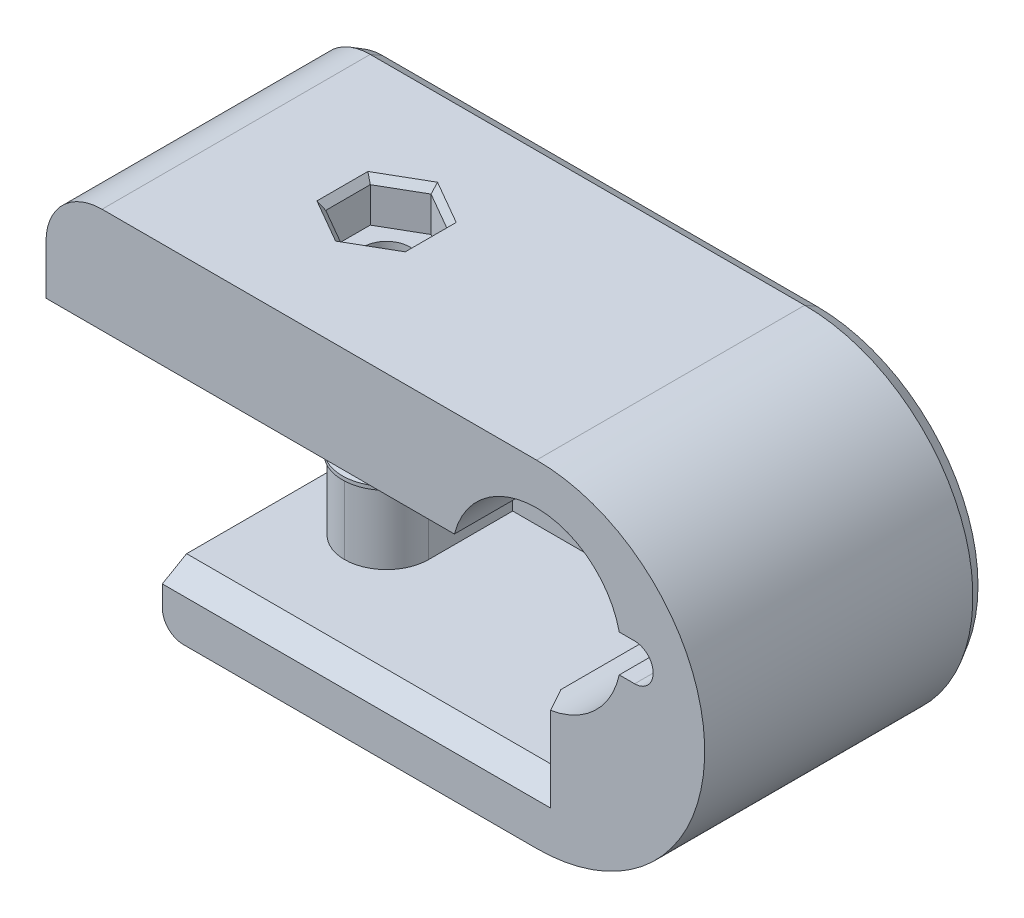
SolidWorks part; units mm, degrees
material "Custom Plastic"
ref_plane "Front Plane" through (0, 0, 0) normal (0, 0, 1) x (1, 0, 0)
ref_plane "Top Plane" through (0, 0, 0) normal (0, 1, 0) x (1, 0, 0)
ref_plane "Right Plane" through (0, 0, 0) normal (1, 0, 0) x (0, 0, -1)
sketch "Sketch1" plane through (0, 0, 0) normal (0, 0, 1) x (1, 0, 0)
  line L0 (5.9035, -1.3233) -> (7, -1.3233)
  line L1 (0, 9) -> (-31, 9)
  line L3 (0, -15) -> (-26.7, -15)
  line L4 (-26.7, -6) -> (-26.7, -15)
  line L5 (-41.6611, -6) -> (7.1, -6) construction
  line L6 (-41.6611, -6) -> (-41.6611, -11) construction
  line L7 (-41.6611, -11) -> (7.1, -11) construction
  line L8 (7.1, -6) -> (7.1, -11) construction
  line L9 (-20, 15.6207) -> (-20, -19.311) construction
  line L10 (7, 1.3233) -> (5.9035, 1.3233)
  line L11 (-25, -4.25) -> (-15, -4.25) construction
  line L12 (-25, -4.25) -> (-25, -0.25) construction
  line L13 (-15, -4.25) -> (-15, -0.25) construction
  line L14 (-25, -0.25) -> (-15, -0.25) construction
  line L15 (-25, -4.25) -> (-15, -0.25) construction
  line L16 (-15, -4.25) -> (-25, -0.25) construction
  line L17 (-5.8611, -1.5) -> (-10.9, -6)
  line L18 (-10.9, -6) -> (-26.7, -6)
  line L20 (-5.8611, 1.5) -> (-35, 1.5)
  line L21 (-35, 1.5) -> (-35, 5)
  arc A0 (5.9035, 1.3233) -> (-5.8611, 1.5) centre (0, 0) ccw
  arc A1 (7, -1.3233) -> (7, 1.3233) centre (7, 0) ccw
  arc A2 (-5.8611, -1.5) -> (5.9035, -1.3233) centre (0, 0) ccw
  arc A3 (0, -15) -> (0, 9) centre (0, -3) ccw
  arc A4 (-31, 9) -> (-35, 5) centre (-31, 5) ccw
  point P18 (-20, -2.25)
  dimension "D1" = 12.1
  dimension "D12" = 12
  dimension "D16" = 4
  dimension "D3" = 5
  dimension "D4" = 7.1
  dimension "D5" = 20
  dimension "D6" = 4
  dimension "D7" = 10
  dimension "D8" = 1.75
  dimension "D9" = 4
  dimension "D10" = 10.9
  dimension "D11" = 1.75
  dimension "D13" = 7
  dimension "D14" = 35
  dimension "D15" = 1.7
  dimension "D2" = 6
extrude "Boss-Extrude1" add sketch "Sketch1" along normal blind 20
sketch "Sketch2" plane through (0, 0, 20) normal (0, 0, 1) x (1, 0, 0)
  line L0 (-26.7, -6) -> (-26.7, -15) construction
  line L1 (-26.7, -6) -> (-23.7, -6)
  line L2 (-26.7, -6) -> (-26.7, -11)
  line L3 (-26.7, -11) -> (-23.7, -11)
  line L6 (-20.7, -18.4336) -> (-20.7, 0) construction
  line L7 (-17.7, -11) -> (-17.7, -6)
  line L8 (-23.7, -11) -> (-23.7, -6)
  line L9 (-17.7, -11) -> (0, -11)
  line L10 (-17.7, -18.4336) -> (-17.7, 0) construction
  line L11 (-23.7, -18.4336) -> (-23.7, 0) construction
  line L12 (-17.7, -6) -> (-10.9, -6)
  line L14 (0, 0) -> (-5.8611, -1.5)
  line L15 (-5.8611, -1.5) -> (-10.9, -6)
  line L16 (0, 0) -> (0, -11)
  dimension "D4" = 20.7
  dimension "D1" = 5
  dimension "D5" = 3
  dimension "D6" = 3
extrude "Cut-Extrude1" cut sketch "Sketch2" against normal offset from surface (16 mm away) 4 up to face at (-9.8986, -1.1908, 0)
sketch "Sketch3" plane through (0, 0, 20) normal (0, 0, 1) x (1, 0, 0)
  line L1 (-23.7, -11) -> (-17.7, -11)
  line L2 (-23.7, -11) -> (-23.7, -6)
  line L3 (-23.7, -6) -> (-17.7, -6)
  line L4 (-17.7, -11) -> (-17.7, -6)
extrude "Cut-Extrude2" cut sketch "Sketch3" against normal blind 7
fillet "Fillet1" radius 3 2 edges at (-17.7, -8.5, 13) (-23.7, -8.5, 13)
sketch "Sketch4" plane through (-1.2719, 0, 0) normal (0, 1, 0) x (1, 0, 0)
  circle A0 centre (-19.4281, -10) radius 1.65
  circle A1 centre (-19.4281, -10) radius 3 construction
  dimension "D1" = 3.3
extrude "Cut-Extrude3" cut sketch "Sketch4" against normal through all and the other way through all
sketch "Sketch5" plane through (-1.2719, 0, 0) normal (0, 1, 0) x (1, 0, 0)
  line L1 (-19.4281, -13.1754) -> (-16.6781, -11.5877)
  line L2 (-16.6781, -11.5877) -> (-16.6781, -8.4123)
  line L3 (-16.6781, -8.4123) -> (-19.4281, -6.8246)
  line L4 (-19.4281, -6.8246) -> (-22.1781, -8.4123)
  line L5 (-22.1781, -8.4123) -> (-22.1781, -11.5877)
  line L6 (-22.1781, -11.5877) -> (-19.4281, -13.1754)
  circle A0 centre (-19.4281, -10) radius 2.75 construction
  circle A1 centre (-19.4281, -10) radius 1.65 construction
  dimension "D1" = 5.5
extrude "Cut-Extrude4" cut sketch "Sketch5" against normal offset from surface (10 mm away) 21 from offset 16 up to face at (-20.7, -15, 11.65)
fillet "Fillet2" [suppressed] radius 12
fillet "Fillet3" radius 1.5 1 edges at (-26.7, -15, 10)
sketch "Sketch6" plane through (0, 1.5, 0) normal (0, -1, 0) x (1, 0, 0)
  line L0 (-17.7, 2.476) -> (-17.7, 5.8757) construction
  line L1 (-17.7, 4) -> (-17.7, 10) construction
  line L2 (-23.7, 2.476) -> (-23.7, 5.8757) construction
  line L3 (-23.7, 4) -> (-23.7, 10) construction
  circle A0 centre (-20.7, 10) radius 3.15
  circle A1 centre (-20.7, 10) radius 1.65
  circle A2 centre (-20.7, 10) radius 1.65 construction
  arc A3 (-23.7, 5.8757) -> (-17.7, 5.8757) centre (-20.7, 10) ccw construction
  arc A4 (-23.7, 2.476) -> (-17.7, 2.476) centre (-20.7, 10) ccw construction
  dimension "D1" = 1.5
  dimension "D2" = 5.1
  dimension "D3" = 3
extrude "Boss-Extrude2" add sketch "Sketch6" along normal blind 1.75
sketch "Sketch7" plane through (0, -6, 0) normal (0, 1, 0) x (1, 0, 0)
  line L0 (-23.7, -5.8757) -> (-23.7, -2.476) construction
  line L1 (-23.7, -4) -> (-23.7, -10) construction
  line L2 (-17.7, -2.476) -> (-17.7, -5.8757) construction
  line L3 (-17.7, -4) -> (-17.7, -10) construction
  circle A0 centre (-20.7, -10) radius 1.65
  circle A1 centre (-20.7, -10) radius 3.15
  circle A2 centre (-20.7, -10) radius 1.65 construction
  arc A3 (-17.7, -5.8757) -> (-23.7, -5.8757) centre (-20.7, -10) ccw construction
  arc A4 (-17.7, -2.476) -> (-23.7, -2.476) centre (-20.7, -10) ccw construction
  dimension "D1" = 1.5
  dimension "D2" = 5.1
  dimension "D3" = 3
extrude "Boss-Extrude3" add sketch "Sketch7" along normal blind 1.75
chamfer "Chamfer1" distance 1.5 angle 40 2 edges at (-23.85, -4.25, 10) (-17.55, -0.25, 10) first distance on face at (-23.85, -4.25, 10) first distance on face at (-17.55, -0.25, 10)
chamfer "Chamfer2" distance 1.875 angle 45 1 edges at (-20.7, -15, 11.65)
chamfer "Chamfer3" distance 1 angle 60 2 edges at (-13.35, -11, 20) (0, -8.525, 20) first distance on face at (-9.7714, -2.762, 20)
chamfer "Chamfer4" distance 0.5 angle 60 15 edges at (12, -3, 0) (-15.5, 9, 0) (-33.8284, 7.8284, 0) (-35, 3.25, 0) (-20.4306, 1.5, 0) (0.0908, 6.0493, 0) (6.4517, 1.3233, 0) (8.3233, 0, 0) (6.4517, -1.3233, 0) (0.0908, -6.0493, 0) (-8.3806, -3.75, 0) (-18.8, -6, 0) (-26.7, -9.75, 0) (-26.2607, -14.5607, 0) (-12.6, -15, 0) first distance on face at (-10.9394, -2.0321, 0)
chamfer "Chamfer6" distance 0.3 distance2 1 1 edges at (-26.7, -8.5, 4) first distance on face at (-25.2, -8.5, 4)
sketch "Sketch8" plane through (0, -6, 0) normal (0, 1, 0) x (1, 0, 0)
  line L0 (-23.7, -5.8757) -> (-23.7, -3.5649)
  line L1 (-17.7, -5.8757) -> (-17.7, -3.5649)
  line L2 (-17.7, -4) -> (-17.7, -9.0395) construction
  line L5 (-23.7, -4) -> (-23.7, -9.0395) construction
  arc A0 (-17.7, -5.8757) -> (-23.7, -5.8757) centre (-20.7, -10) ccw
  arc A1 (-17.7, -3.5649) -> (-23.7, -3.5649) centre (-20.7, -10) ccw
  dimension "D1" = 10.2
  dimension "D2" = 2
extrude "Boss-Extrude4" add sketch "Sketch8" along normal blind 0.5
sketch "Sketch9" plane through (0, 1.5, 0) normal (0, -1, 0) x (1, 0, 0)
  line L0 (-23.7, 3.5649) -> (-23.7, 5.8757)
  line L1 (-17.7, 3.5649) -> (-17.7, 5.8757)
  arc A0 (-23.7, 5.8757) -> (-17.7, 5.8757) centre (-20.7, 10) ccw
  arc A1 (-23.7, 3.5649) -> (-17.7, 3.5649) centre (-20.7, 10) ccw
  arc A2 (-23.7, 5.8757) -> (-17.7, 5.8757) centre (-20.7, 10) ccw construction
  arc A3 (-23.7, 3.5649) -> (-17.7, 3.5649) centre (-20.7, 10) ccw construction
extrude "Boss-Extrude5" add sketch "Sketch9" along normal blind 0.5
chamfer "Chamfer7" distance 0.5 angle 70 6 edges at (-17.7, -5.5, 4.7203) (-23.7, -5.5, 4.7203) (-20.7, -5.5, 2.9) (-17.7, 1, 4.7203) (-23.7, 1, 4.7203) (-20.7, 1, 2.9) first distance on face at (-17.7, -7, 6.2134) first distance on face at (-23.7, -7, 6.2134) first distance on face at (-20.7, -5.75, 3.2325) first distance on face at (-17.7, 1.25, 4.7203) first distance on face at (-23.7, 1.25, 4.7203) first distance on face at (-20.7, 1.25, 3.2325)
chamfer "Chamfer8" distance 0.5 distance2 0.4 6 edges at (-22.075, 9, 12.3816) (-19.325, 9, 12.3816) (-17.95, 9, 10) (-19.325, 9, 7.6184) (-22.075, 9, 7.6184) (-23.45, 9, 10) first distance on face at (-22.075, 7.5, 12.3816) first distance on face at (-19.325, 7.5, 12.3816) first distance on face at (-17.95, 7.5, 10) first distance on face at (-19.325, 7.5, 7.6184) first distance on face at (-22.075, 7.5, 7.6184) first distance on face at (-23.45, 7.5, 10)
sketch "Sketch10" plane through (0, 6, 0) normal (0, 1, 0) x (1, 0, 0)
  line L0 (-20.7, -10) -> (-19.5333, -11.1667)
  line L1 (-19.5333, -11.1667) -> (-20.3365, -11.97)
  line L2 (-20.3365, -11.97) -> (-21.0635, -11.97)
  line L3 (-21.0635, -11.97) -> (-21.8667, -11.1667)
  line L4 (-21.8667, -11.1667) -> (-20.7, -10)
  line L5 (-20.7, -10) -> (-20.7, -11.97) construction
  circle A0 centre (-20.7, -10) radius 1.65 construction
  point P8 (-20.7, -11.65)
  dimension "D1" = 0.32
extrude "Cut-Extrude5" cut sketch "Sketch10" against normal through all
equation "\"y-plate-thickness\"=5"
equation "\"bed-plate-thickness\"=6"
equation "\"x-plate-thickness\"=5"
equation "\"D3@Sketch1\"=\"x-plate-thickness\""
equation "\"rod-diameter\"=12"
equation "\"D2@Sketch1\"=\"rod-diameter\"/2"
equation "\"D1@Sketch2\"=\"x-plate-thickness\""
equation "\"D1@Sketch1\"=\"rod-diameter\"+0.1"
equation "\"D12@Sketch1\"=\"rod-diameter\""
equation "\"D14@Sketch1\"=\"x-plate-thickness\"+30"
equation "\"y-cross-rib-thickness\"=6"
equation "\"y-rib-thickness\"=6"
equation "\"t-nut-hole-diameter\"=3"
equation "\"enclosure-thickness\"=0.6"
equation "\"M3-Clearance\"=3.3"
equation "\"M4-Clearance\"=4.3"
equation "\"M5-Clearance\"=5.3"
equation "\"M6-Clearance\"=6.3"
equation "\"M8-Clearance\"=8.3"
equation "\"623-Bearing-Dia\"=11.2"
